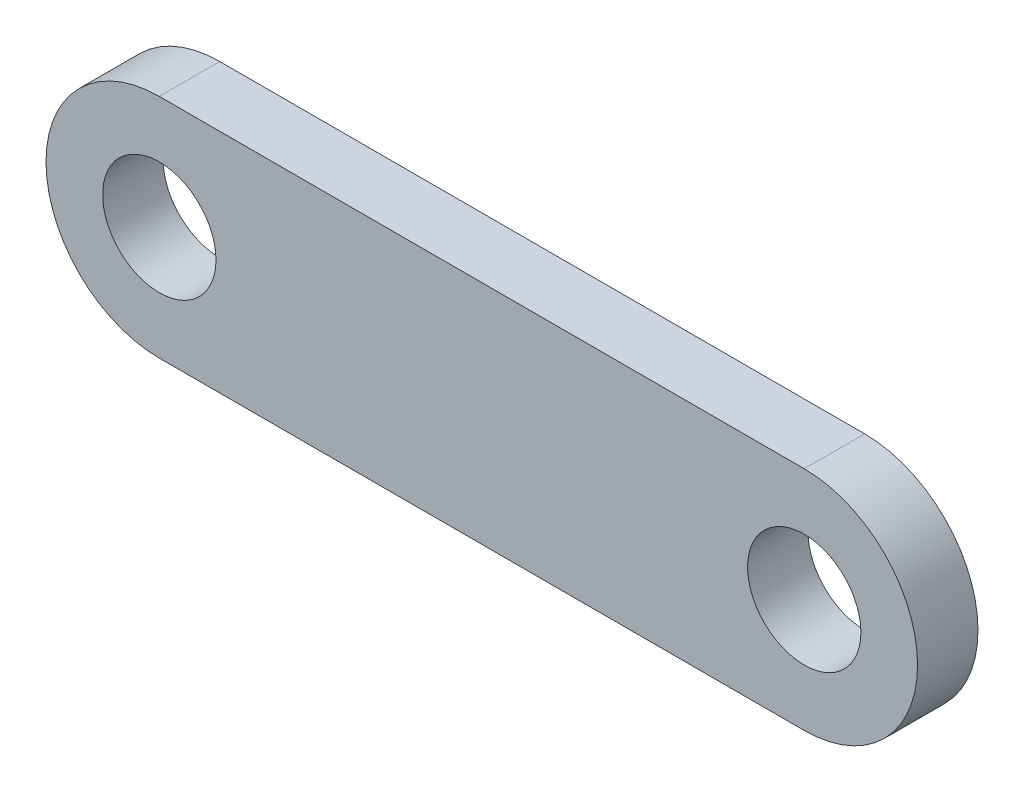
SolidWorks part; units mm, degrees
material "ABS"
ref_plane "Front Plane" through (0, 0, 0) normal (0, 0, 1) x (1, 0, 0)
ref_plane "Top Plane" through (0, 0, 0) normal (0, 1, 0) x (1, 0, 0)
ref_plane "Right Plane" through (0, 0, 0) normal (1, 0, 0) x (0, 0, -1)
sketch "Sketch1" plane through (0, 0, 0) normal (0, 0, 1) x (1, 0, 0)
  line L0 (0, 4.7625) -> (27.1018, 4.7625)
  line L1 (0, -4.7625) -> (27.1018, -4.7625)
  circle A0 centre (0, 0) radius 2.3813
  circle A1 centre (0, 0) radius 4.7625
  circle A2 centre (27.1018, 0) radius 2.3813
  circle A3 centre (27.1018, 0) radius 4.7625
  dimension "D1" = 4.7625
  dimension "D2" = 9.525
extrude "Boss-Extrude2" add sketch "Sketch1" along normal blind 2.54 contours A1 A0 | A3 A2 | A3 L0 A1 L1 region at (13.5509, 0, 0) region at (3.2723, 3.2723, 0) region at (30.3741, 3.2723, 0)
